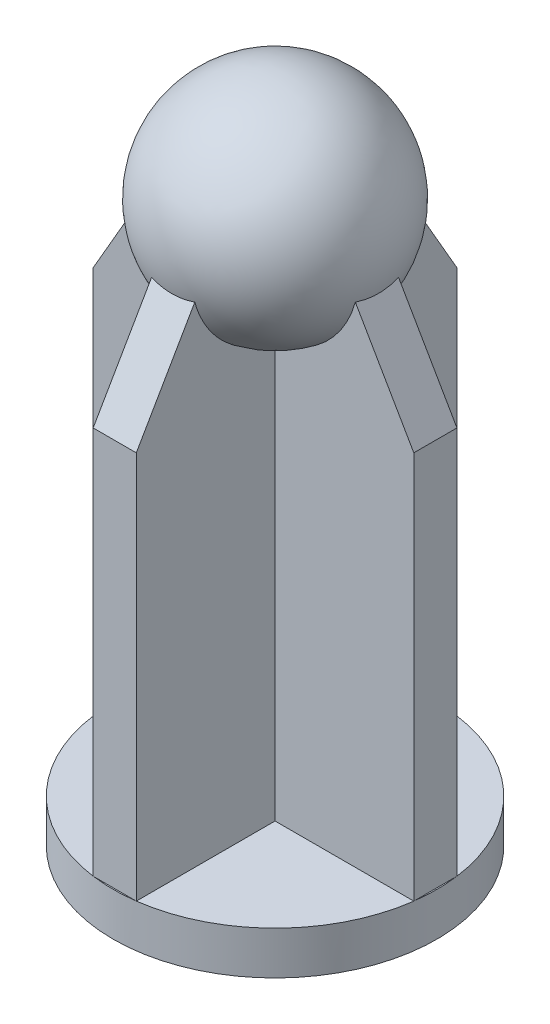
SolidWorks part; units mm, degrees
ref_plane "Front Plane" through (0, 0, 0) normal (0, 0, 1) x (1, 0, 0)
ref_plane "Top Plane" through (0, 0, 0) normal (0, 1, 0) x (1, 0, 0)
ref_plane "Right Plane" through (0, 0, 0) normal (1, 0, 0) x (0, 0, -1)
sketch "Sketch1" plane through (0, 0, 0) normal (0, 1, 0) x (1, 0, 0)
  circle A0 centre (0, 0) radius 37.5
  dimension "D1" = 75
extrude "Boss-Extrude1" add sketch "Sketch1" along normal blind 10
ref_plane "Plane1" through (0, 130, 0) normal (0, 1, 0) x (1, 0, 0)
sketch "Sketch4" plane through (0, 130, 0) normal (0, 1, 0) x (1, 0, 0)
  line L0 (0, 25) -> (0, -25)
  arc A0 (0, -25) -> (0, 25) centre (0, 0) ccw
  dimension "D1" = 50
revolve "Revolve3" add sketch "Sketch4" angle 360 about L0
sketch "Sketch3" plane through (0, 10, 0) normal (0, 1, 0) x (1, 0, 0)
  line L0 (-5, 5) -> (-5, 37.1652)
  line L1 (-5.1863, 0) -> (5.6185, 0) construction
  line L2 (-5, 37.1652) -> (5, 37.1652)
  line L3 (5, 5) -> (5, 37.1652)
  line L4 (0, 5.624) -> (0, -4.7967) construction
  line L5 (5, 5) -> (37.1652, 5)
  line L6 (5, -5) -> (37.1652, -5)
  line L7 (37.1652, 5) -> (37.1652, -5)
  line L8 (-5.1863, 0) -> (5.6185, 0) construction
  line L9 (-5, -5) -> (-5, -37.1652)
  line L10 (5, -5) -> (5, -37.1652)
  line L11 (-5, -37.1652) -> (5, -37.1652)
  line L12 (0, 5.624) -> (0, -4.7967) construction
  line L13 (-5, 5) -> (-37.1652, 5)
  line L14 (-5, -5) -> (-37.1652, -5)
  line L15 (-37.1652, 5) -> (-37.1652, -5)
  line L16 (0, 37.1652) -> (0, 0) construction
  line L17 (0, 0) -> (37.1652, 0) construction
  line L18 (0, 0) -> (0, -37.1652) construction
  line L20 (-37.1652, 0) -> (0, 0) construction
  circle A2 centre (0, 0) radius 37.5 construction
  dimension "D1" = 10
extrude "Boss-Extrude2" add sketch "Sketch3" along normal blind 120
chamfer "Chamfer1" distance 30 angle 30 4 edges at (37.1652, 130, 0) (0, 130, -37.1652) (-37.1652, 130, 0) (0, 130, 37.1652) first distance on face at (37.1652, 70, 0) first distance on face at (0, 70, -37.1652) first distance on face at (-37.1652, 70, 0) first distance on face at (0, 70, 37.1652)
